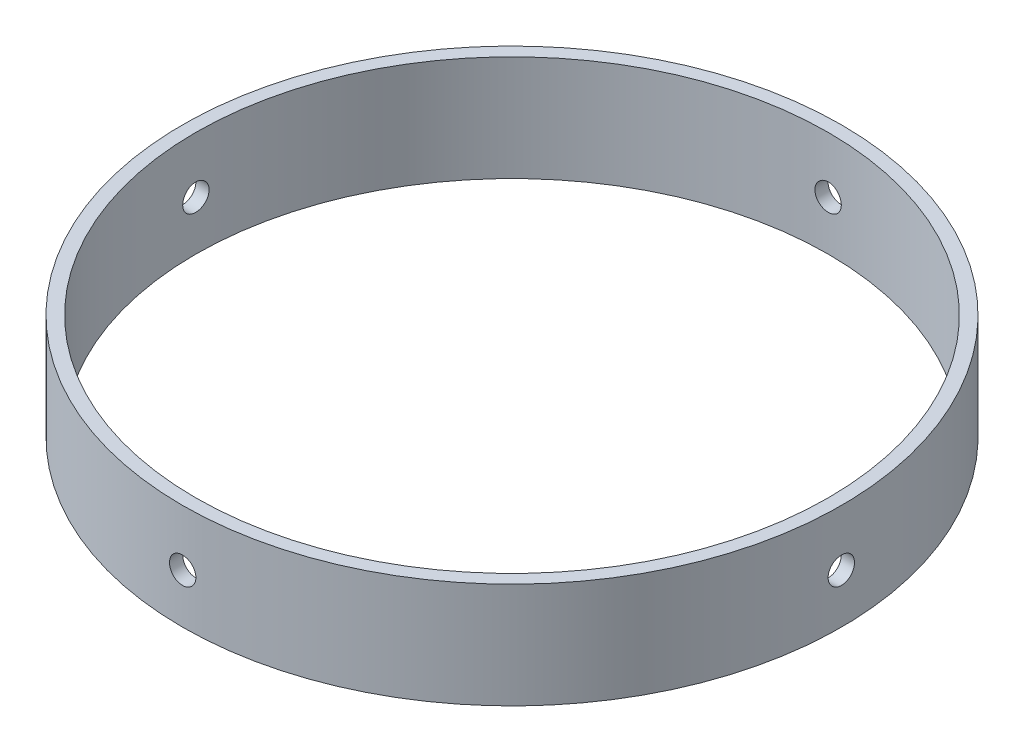
SolidWorks part; units mm, degrees
ref_plane "Front Plane" through (0, 0, 0) normal (0, 0, 1) x (1, 0, 0)
ref_plane "Top Plane" through (0, 0, 0) normal (0, 1, 0) x (1, 0, 0)
ref_plane "Right Plane" through (0, 0, 0) normal (1, 0, 0) x (0, 0, -1)
sketch "Sketch1" plane through (0, 0, 0) normal (0, 1, 0) x (1, 0, 0)
  circle A0 centre (0, 0) radius 79.375
  circle A1 centre (0, 0) radius 76.2
  dimension "D1" = 158.75
  dimension "D2" = 152.4
extrude "Boss-Extrude1" add sketch "Sketch1" along normal blind 25.4
ref_plane "Plane1" through (0, 0, 79.375) normal (0, 0, 1) x (1, 0, 0)
sketch "Sketch2" plane through (0, 0, 79.375) normal (0, 0, 1) x (1, 0, 0)
  circle A0 centre (0, 11.8909) radius 3.175
  dimension "D1" = 6.35
ref_axis "Axis1" through (0, 25.4, 0) along (0, -1, 0)
extrude "Cut-Extrude4" cut sketch "Sketch2" against normal up to next
pattern_circular "CirPattern1" count 4 over 360 about axis through (0, 25.4, 0) along (0, -1, 0) of "Cut-Extrude4"
ref_axis "Axis2" through (0, 11.8909, 75.9546) along (0, 0, 1)
ref_axis "Axis3" through (-75.9546, 11.8909, 0) along (-1, 0, 0)
ref_plane "Plane2" through (-76.2, 0, 0) normal (1, 0, 0) x (0, 0, -1)
